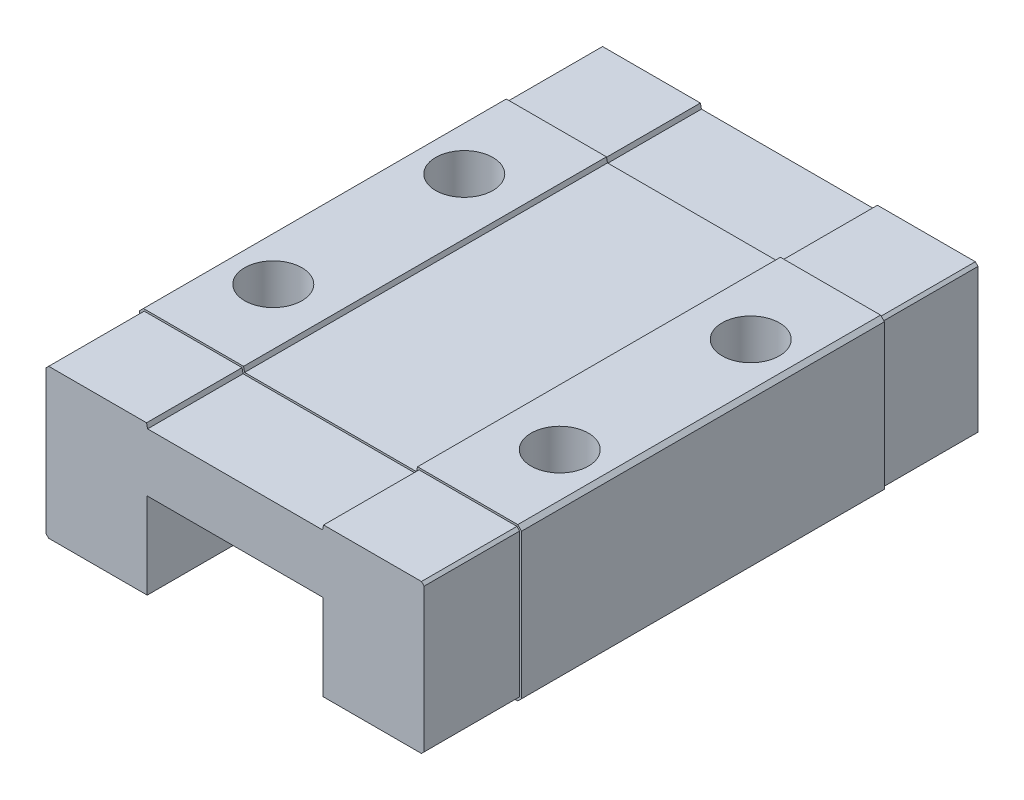
SolidWorks part; units mm, degrees
material "1.4000 (X6Cr13)"
ref_plane "Alzado" through (0, 0, 0) normal (0, 0, 1) x (1, 0, 0)
ref_plane "Planta" through (0, 0, 0) normal (0, 1, 0) x (1, 0, 0)
ref_plane "Vista lateral" through (0, 0, 0) normal (1, 0, 0) x (0, 0, -1)
sketch "Croquis1" plane through (0, 0, 0) normal (0, 0, 1) x (1, 0, 0)
  line L0 (-9.8, 4) -> (-4.555, 4)
  line L1 (-10, -4) -> (10, -4) construction
  line L2 (-10, -4) -> (-10, 4) construction
  line L3 (-10, 4) -> (10, 4) construction
  line L4 (10, -4) -> (10, 4) construction
  line L5 (-10, -4) -> (10, 4) construction
  line L6 (-10, 4) -> (10, -4) construction
  line L7 (-4.555, 4) -> (-4.5, 3.75)
  line L8 (-4.5, 3.75) -> (4.5, 3.75)
  line L9 (0, 5.9288) -> (0, -5.9739) construction
  line L10 (-4.5, -4) -> (-4.5, 0.5)
  line L11 (-4.5, 0.5) -> (4.5, 0.5)
  line L12 (-10, 3.8) -> (-10, -3.8)
  line L13 (-9.8, -4) -> (-4.5, -4)
  line L14 (-10, 3.8) -> (-9.8, 4)
  line L15 (-10, -3.8) -> (-9.8, -4)
  line L16 (4.5, -4) -> (4.5, 0.5)
  line L17 (9.8, -4) -> (4.5, -4)
  line L18 (10, -3.8) -> (9.8, -4)
  line L19 (10, 3.8) -> (10, -3.8)
  line L20 (10, 3.8) -> (9.8, 4)
  line L21 (9.8, 4) -> (4.555, 4)
  line L22 (4.555, 4) -> (4.5, 3.75)
  line L24 (-4.5, -6) -> (4.5, -6) construction
  line L25 (-4.5, -6) -> (-4.5, 0.5) construction
  line L26 (-4.5, 0.5) -> (4.5, 0.5) construction
  line L27 (4.5, -6) -> (4.5, 0.5) construction
  line L28 (-4.5, -6) -> (4.5, 0.5) construction
  line L29 (-4.5, 0.5) -> (4.5, -6) construction
  point P0 (0, 0)
  point P9 (0, -2.75)
  point P19 (0, 0.5)
  point P26 (0, 3.75)
  dimension "D1" = 20
  dimension "D2" = 2
  dimension "D3" = 0.25
  dimension "D4" = 5.5
  dimension "D5" = 6.5
  dimension "D6" = 4.5
  dimension "D7" = 10
extrude "Saliente-Extruir1" add sketch "Croquis1" along normal blind 29
sketch "Croquis2" plane through (0, 4, 0) normal (0, 1, 0) x (1, 0, 0)
  line L0 (-10, -14.5) -> (14.8854, -14.5) construction
  line L1 (-10, -29) -> (-10, 0) construction
  line L2 (0, 0) -> (0, -45.7286) construction
  line L3 (4.5, 0) -> (-4.5, 0) construction
  circle A0 centre (-7.5, -19.5) radius 1.5
  circle A1 centre (7.5, -19.5) radius 1.5
  circle A2 centre (7.5, -9.5) radius 1.5
  circle A3 centre (-7.5, -9.5) radius 1.5
  dimension "D3" = 5
  dimension "D4" = 7.5
  dimension "D5" = 3
  dimension "D1" = 2
  dimension "D2" = 2
extrude "Cortar-Extruir1" cut sketch "Croquis2" against normal blind 3.5
sketch "Croquis4" plane through (0, 0, 29) normal (0, 0, 1) x (1, 0, 0)
  line L36 (9.7586, -3.9) -> (9.9, -3.7586)
  line L37 (9.9, -3.7586) -> (9.9, 3.7586)
  line L38 (4.6, -3.9) -> (9.7586, -3.9)
  line L39 (4.6, 0.5) -> (4.6, -3.9)
  line L40 (9.9, 3.7586) -> (9.7293, 3.9293)
  line L41 (9.7586, -3.9) -> (9.9, -3.7586)
  line L42 (9.9, -3.7586) -> (9.9, 3.7586)
  line L43 (4.6, -3.9) -> (9.7586, -3.9)
  line L44 (4.6, 0.6) -> (4.6, -3.9)
  line L45 (9.9, 3.7586) -> (9.7586, 3.9)
  line L88 (9.8, 3.9) -> (4.6354, 3.9)
  line L89 (4.6354, 3.9) -> (4.5804, 3.65)
  line L90 (-4.6, 0.6) -> (4.5, 0.6)
  line L91 (-4.6, -3.9) -> (-4.6, 0.6)
  line L92 (-9.7586, -3.9) -> (-4.6, -3.9)
  line L93 (-9.9, -3.7586) -> (-9.7586, -3.9)
  line L94 (-9.9, 3.7586) -> (-9.9, -3.7586)
  line L95 (-9.7586, 3.9) -> (-9.9, 3.7586)
  line L96 (-4.6354, 3.9) -> (-9.7586, 3.9)
  line L97 (4.5804, 3.65) -> (-4.5804, 3.65)
  line L98 (-4.5804, 3.65) -> (-4.6354, 3.9)
  line L99 (9.7586, 3.9) -> (4.6354, 3.9)
  line L100 (4.6354, 3.9) -> (4.5804, 3.65)
  line L101 (-4.6, 0.6) -> (4.6, 0.6)
  line L102 (-4.6, -3.9) -> (-4.6, 0.6)
  line L103 (-9.7586, -3.9) -> (-4.6, -3.9)
  line L104 (-9.9, -3.7586) -> (-9.7586, -3.9)
  line L105 (-9.9, 3.7586) -> (-9.9, -3.7586)
  line L106 (-9.7586, 3.9) -> (-9.9, 3.7586)
  line L107 (-4.6354, 3.9) -> (-9.7586, 3.9)
  line L108 (4.5804, 3.65) -> (-4.5804, 3.65)
  line L109 (-4.5804, 3.65) -> (-4.6354, 3.9)
  dimension "D1" = 0.1
  dimension "D2" = 0.1
extrude "Cortar-Extruir2" cut sketch "Croquis4" against normal blind 5 flip side to cut
sketch "Croquis5" plane through (0, 0, 0) normal (0, 0, -1) x (-1, 0, 0)
  line L37 (4.6354, 3.9) -> (4.5804, 3.65)
  line L38 (4.5804, 3.65) -> (-4.5804, 3.65)
  line L39 (-4.5804, 3.65) -> (-4.6354, 3.9)
  line L40 (-4.6354, 3.9) -> (-9.7586, 3.9)
  line L46 (-9.7586, 3.9) -> (-9.9, 3.7586)
  line L47 (-9.9, 3.7586) -> (-9.9, -3.7586)
  line L48 (-9.9, -3.7586) -> (-9.7586, -3.9)
  line L49 (-9.7586, -3.9) -> (-4.6, -3.9)
  line L50 (-4.6, -3.9) -> (-4.6, 0.6)
  line L51 (-4.6, 0.6) -> (4.6, 0.6)
  line L52 (4.6, 0.6) -> (4.6, -3.9)
  line L53 (4.6, -3.9) -> (9.7586, -3.9)
  line L54 (9.7586, -3.9) -> (9.9, -3.7586)
  line L55 (9.9, -3.7586) -> (9.9, 3.7586)
  line L56 (9.9, 3.7586) -> (9.7586, 3.9)
  line L57 (9.7586, 3.9) -> (4.6354, 3.9)
  line L58 (4.6354, 3.9) -> (4.5804, 3.65)
  line L59 (4.5804, 3.65) -> (-4.5804, 3.65)
  line L60 (-4.5804, 3.65) -> (-4.6354, 3.9)
  line L61 (-4.6354, 3.9) -> (-9.7586, 3.9)
  line L62 (-9.7586, 3.9) -> (-9.9, 3.7586)
  line L63 (-9.9, 3.7586) -> (-9.9, -3.7586)
  line L64 (-9.9, -3.7586) -> (-9.7586, -3.9)
  line L65 (-9.7586, -3.9) -> (-4.6, -3.9)
  line L66 (-4.6, -3.9) -> (-4.6, 0.6)
  line L67 (-4.6, 0.6) -> (4.6, 0.6)
  line L68 (4.6, 0.6) -> (4.6, -3.9)
  line L69 (4.6, -3.9) -> (9.7586, -3.9)
  line L70 (9.7586, -3.9) -> (9.9, -3.7586)
  line L71 (9.9, -3.7586) -> (9.9, 3.7586)
  line L72 (9.9, 3.7586) -> (9.7586, 3.9)
  line L73 (9.7586, 3.9) -> (4.6354, 3.9)
  dimension "D1" = 0.1
extrude "Cortar-Extruir3" cut sketch "Croquis5" against normal blind 5 flip side to cut
sketch "Croquis6" plane through (0, 0, 5) normal (0, 0, -1) x (-1, 0, 0)
  line L0 (10, -3.8) -> (10, 3.8) construction
  line L1 (10, 0.5) -> (9.91, 0.5)
  line L2 (10, 0.5) -> (10, 0)
  line L3 (10, 0) -> (9.91, 0)
  line L4 (9.91, 0.5) -> (9.91, 0)
  line L6 (4.5, -4) -> (9.8, -4) construction
  dimension "D1" = 4
  dimension "D2" = 0.5
  dimension "D3" = 0.09
extrude "Cortar-Extruir5" cut sketch "Croquis6" against normal up to next
sketch "Sketch1" plane through (10, 0, 0) normal (1, 0, 0) x (0, 0, -1)
  text T0 "MGN9C" font "Century Gothic" height in points 9
wrap "Wrap1" sketch "Sketch1" wrap type scribe source sketch "Sketch1" face at (-10, -1.9, 14.5)
ref_plane "Plane1" through (0, 0, 14.5) normal (0, 0, -1) x (-1, 0, 0)
